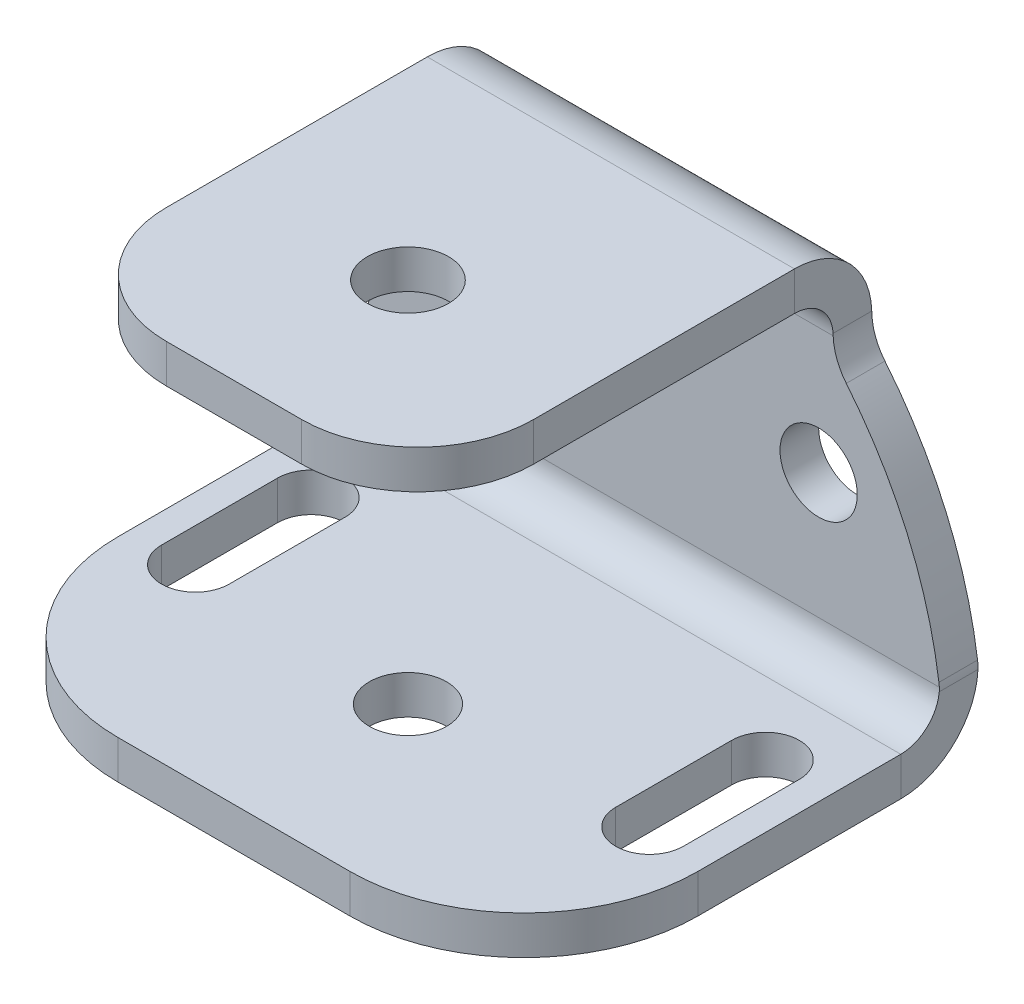
SolidWorks part; units mm, degrees
note: The reader was unsure of these and kept them because the rebuilt part matched: flange length of "Brida de arista1", "Brida de arista2".
material "acero"
ref_plane "Alzado" through (0, 0, 0) normal (0, 0, 1) x (1, 0, 0)
ref_plane "Planta" through (0, 0, 0) normal (0, 1, 0) x (1, 0, 0)
ref_plane "Vista lateral" through (0, 0, 0) normal (1, 0, 0) x (0, 0, -1)
sketch "Croquis1" plane through (0, 0, 0) normal (0, 0, 1) x (1, 0, 0)
  line L0 (0, 0) -> (30, 0)
  line L1 (30, 0) -> (24.5, 17) construction
  line L2 (24.5, 17) -> (5.5, 17)
  line L3 (5.5, 17) -> (0, 0) construction
  line L4 (15, 0) -> (15, 17) construction
  line L5 (0.1926, 3.844) -> (3.2607, 13.3271) construction
  line L6 (25.6845, 16.5876) -> (31.1467, -0.2957) construction
  line L7 (5.5, 17) -> (5.5, 14)
  line L8 (0, 0) -> (0, 2)
  line L9 (24.5, 17) -> (24.5, 14)
  line L10 (30, 0) -> (30, 2)
  arc A0 (24.5, 14) -> (30, 2) centre (8.1108, -0.7721) cw
  arc A2 (0, 2) -> (5.5, 14) centre (21.8892, -0.7721) cw
  dimension "D6" = 2
  dimension "D1" = 30
  dimension "D2" = 17
  dimension "D3" = 19
  dimension "D4" = 1
  dimension "D5" = 1
  dimension "D8" = 2
  dimension "D9" = 3
base flange "Brida base1" sketch "Croquis1" thickness 2 reverse thickness direction no parameters "D1"=0.7366
edge flange "Brida de arista1" sketch "Croquis8" flange angle 90 flange length 21.5 flange position material outside bend radius 2 thickness 2 relief rectangular parameters "D6"=10
sketch "Croquis8" plane through (0, 0, 0) normal (0, -1, 0) x (1, 0, 0)
  line L0 (0, 0) -> (30, 0) construction
  line L1 (0, 0) -> (30, 0)
  line L2 (0, 0) -> (0, 21.5)
  line L3 (0, 21.5) -> (30, 21.5)
  line L4 (30, 21.5) -> (30, 0)
  line L5 (0, -2) -> (30, -2) construction
  dimension "D1" = 23.5
bend "Pliegue de arista5" bend radius 2 bend angle 90 parameters "D5"=1
edge flange "Brida de arista2" sketch "Croquis11" flange angle 90 flange length 21.5 flange position material outside bend radius 2 thickness 2 relief rectangular parameters "D6"=10
sketch "Croquis11" plane through (0, 17, 0) normal (0, 1, 0) x (-1, 0, 0)
  line L0 (-24.5, 0) -> (-5.5, 0) construction
  line L1 (-24.5, 0) -> (-5.5, 0)
  line L2 (-24.5, 0) -> (-24.5, 21.5)
  line L4 (-5.5, 21.5) -> (-5.5, 0)
  line L5 (-5.5, 21.5) -> (-24.5, 21.5)
  line L6 (-30, 21.5) -> (0, 21.5) construction
bend "Pliegue de arista2" bend radius 2 bend angle 90 parameters "D5"=2
sketch "Croquis12" plane through (0, -2, 0) normal (0, 1, 0) x (1, 0, 0)
  line L0 (15, -21.5) -> (15, 2) construction
  line L1 (5.5, -21.5) -> (24.5, -21.5) construction
  line L2 (24.5, 2) -> (5.5, 2) construction
  circle A0 centre (15, -12.5) radius 2
  dimension "D1" = 4
  dimension "D2" = 14.5
extrude "Cortar-Extruir1" cut sketch "Croquis12" along normal up to next normal cut yes
sketch "Croquis13" plane through (0, 0, 0) normal (0, 1, 0) x (1, 0, 0)
  line L0 (15, -2) -> (15, -21.5) construction
  line L1 (24.5, -2) -> (5.5, -2) construction
  line L2 (15, -11.75) -> (9.8308, -11.75) construction
  line L3 (3.25, -5.75) -> (3.25, -11.75) construction
  line L4 (5, -5.75) -> (5, -11.75)
  line L5 (1.5, -5.75) -> (1.5, -11.75)
  line L6 (30, -21.5) -> (0, -21.5) construction
  line L8 (26.75, -5.75) -> (26.75, -11.75) construction
  line L9 (25, -5.75) -> (25, -11.75)
  line L10 (28.5, -5.75) -> (28.5, -11.75)
  arc A0 (5, -5.75) -> (1.5, -5.75) centre (3.25, -5.75) ccw
  arc A1 (1.5, -11.75) -> (5, -11.75) centre (3.25, -11.75) ccw
  arc A2 (25, -5.75) -> (28.5, -5.75) centre (26.75, -5.75) cw
  arc A3 (28.5, -11.75) -> (25, -11.75) centre (26.75, -11.75) cw
  circle A4 centre (15, -12.5) radius 2 construction
  point P8 (3.25, -8.75)
  point P17 (26.75, -8.75)
  dimension "D2" = 1.75
  dimension "D4" = 0.75
  dimension "D1" = 6
  dimension "D3" = 11.75
extrude "Cortar-Extruir2" cut sketch "Croquis13" against normal up to next normal cut yes
sketch "Croquis26" plane through (0, 0, -2) normal (0, 0, -1) x (-1, 0, 0)
  line L0 (-15, 15) -> (-15, 2) construction
  line L1 (-24.5, 15) -> (-5.5, 15) construction
  line L2 (-6.25, 8.5) -> (-15, 8.5) construction
  line L3 (-30, 2) -> (0, 2) construction
  circle A1 centre (-6.25, 8.5) radius 2
  circle A2 centre (-23.75, 8.5) radius 2
  dimension "D1" = 4
  dimension "D2" = 8.75
extrude "Cortar-Extruir6" cut sketch "Croquis26" against normal up to next normal cut yes
hole_wizard "Taladro roscado M51" positions "Croquis3D1" profile "Croquis22" tap size "M5" standard "Iso" end condition up to next
sketch3d "Croquis3D1"
  circle A0 centre (15, 0, 12.5) radius 2 construction
  point P5 (15, 19, 12.5)
  point P11 (15, 2, 12.5)
sketch "Croquis22" plane through (15, 19, 12.5) normal (1, 0, 0) x (0, 0, 1)
  line L0 (0, 0) -> (0, 2)
  line L1 (0, 2) -> (2.1, 2)
  line L2 (2.1, 2) -> (2.1, 0)
  line L5 (2.1, 0) -> (0, 0)
  line L11 (0, -6.35) -> (0, 107.95) construction
  dimension "Diámetro de perforador para roscar hasta el siguiente" = 4.2
  dimension "Profundidad de perforador para roscar hasta el siguiente" = 2
cosmetic thread "Rosca de taladro2"
fillet "Redondeo2" radius 9 2 edges at (30, -1, 21.5) (0, -1, 21.5)
fillet "Redondeo3" radius 6 2 edges at (24.5, 18, 21.5) (5.5, 18, 21.5)
fillet "Redondeo4" radius 3 10 edges at (0, 2, -1) (5.5, 14, -1) (24.5, 14, -1) (30, 2, -1) (24.5, 14.5, -2) (5.5, 14.5, 0) (5.5, 14.5, -2) (24.5, 15, -1) (5.5, 15, -1) (24.5, 14.5, 0)
sketch "Líneas de pliegue1" [suppressed] plane through (0, 0, 0) normal (0, 1, 0) x (1, 0, 0)
sketch "Cuadro delimitador1" [suppressed] plane through (0, 0, 0) normal (0, 1, 0) x (1, 0, 0)
sheet metal parameters "Chapa metálica4" thickness 2 parameters "D1"=0.7366
flat pattern "Chapa desplegada4" [suppressed]
sketch "Líneas de pliegue2" plane through (0, 0, 0) normal (0, 1, 0) x (1, 0, 0)
sketch "Cuadro delimitador2" [suppressed] plane through (0, 0, 0) normal (0, 1, 0) x (1, 0, 0)
sheet metal parameters "Chapa metálica5" thickness 2 parameters "D1"=0.7366
flat pattern "Chapa desplegada4" [suppressed]
sketch "Líneas de pliegue2" plane through (0, 0, 0) normal (0, 1, 0) x (1, 0, 0)
sketch "Cuadro delimitador2" [suppressed] plane through (0, 0, 0) normal (0, 1, 0) x (1, 0, 0)
bend of the flat pattern "Aplanar-<Pliegue de arista5>1"
sheet metal parameters "Chapa metálica6" thickness 2 parameters "D1"=0.7366
flat pattern "Chapa desplegada4" [suppressed]
sketch "Líneas de pliegue2" plane through (0, 0, 0) normal (0, 1, 0) x (1, 0, 0)
sketch "Cuadro delimitador2" [suppressed] plane through (0, 0, 0) normal (0, 1, 0) x (1, 0, 0)
bend of the flat pattern "Aplanar-<Pliegue de arista2>1"
bend of the flat pattern "Aplanar-<Pliegue de arista5>2"
sheet metal parameters "Chapa metálica7" thickness 2 parameters "D1"=0.7366
flat pattern "Chapa desplegada4" [suppressed]
sketch "Líneas de pliegue2" plane through (0, 0, 0) normal (0, 1, 0) x (1, 0, 0)
sketch "Cuadro delimitador2" [suppressed] plane through (0, 0, 0) normal (0, 1, 0) x (1, 0, 0)
bend of the flat pattern "Aplanar-<Pliegue de arista2>1"
bend of the flat pattern "Aplanar-<Pliegue de arista5>3"
sheet metal parameters "Chapa metálica8" thickness 2 parameters "D1"=0.7366
flat pattern "Chapa desplegada4" [suppressed]
sketch "Líneas de pliegue2" plane through (0, 0, 0) normal (0, 1, 0) x (1, 0, 0)
sketch "Cuadro delimitador2" [suppressed] plane through (0, 0, 0) normal (0, 1, 0) x (1, 0, 0)
bend of the flat pattern "Aplanar-<Pliegue de arista2>1"
bend of the flat pattern "Aplanar-<Pliegue de arista5>4"
sheet metal parameters "Chapa metálica15" thickness 2 parameters "D1"=0.7366
flat pattern "Chapa desplegada4"
sketch "Líneas de pliegue3" plane through (0, 0, 0) normal (0, 0, 1) x (1, 0, 0)
  line L4 (24.5, 17.3562) -> (5.5, 17.3562) construction
  line L5 (0, -0.3562) -> (30, -0.3562) construction
  line L6 (24.5, 17.3562) -> (5.5, 17.3562) construction
  line L7 (0, -0.3562) -> (30, -0.3562) construction
sketch3d "Cuadro delimitador3" [suppressed]
  line L0 (8.1108, -21.4402, 0) -> (8.1108, 39.9845, 0) construction
  line L1 (-21.8892, -21.4402, 0) -> (-21.8892, 39.9845, 0) construction
  line L2 (8.1108, -21.4402, 0) -> (-21.8892, -21.4402, 0) construction
  line L3 (8.1108, 39.9845, 0) -> (-21.8892, 39.9845, 0) construction
bend of the flat pattern "Aplanar-<Pliegue de arista2>3"
bend of the flat pattern "Aplanar-<Pliegue de arista5>7"
sheet metal parameters "Chapa metálica17" thickness 2 parameters "D1"=0.7366
flat pattern "Chapa desplegada4" [suppressed]
sketch "Líneas de pliegue3" plane through (0, 0, 0) normal (0, 1, 0) x (1, 0, 0)
sketch "Cuadro delimitador3" [suppressed] plane through (0, 0, 0) normal (0, 1, 0) x (1, 0, 0)
bend of the flat pattern "Aplanar-<Pliegue de arista2>2"
bend of the flat pattern "Aplanar-<Pliegue de arista5>6"
